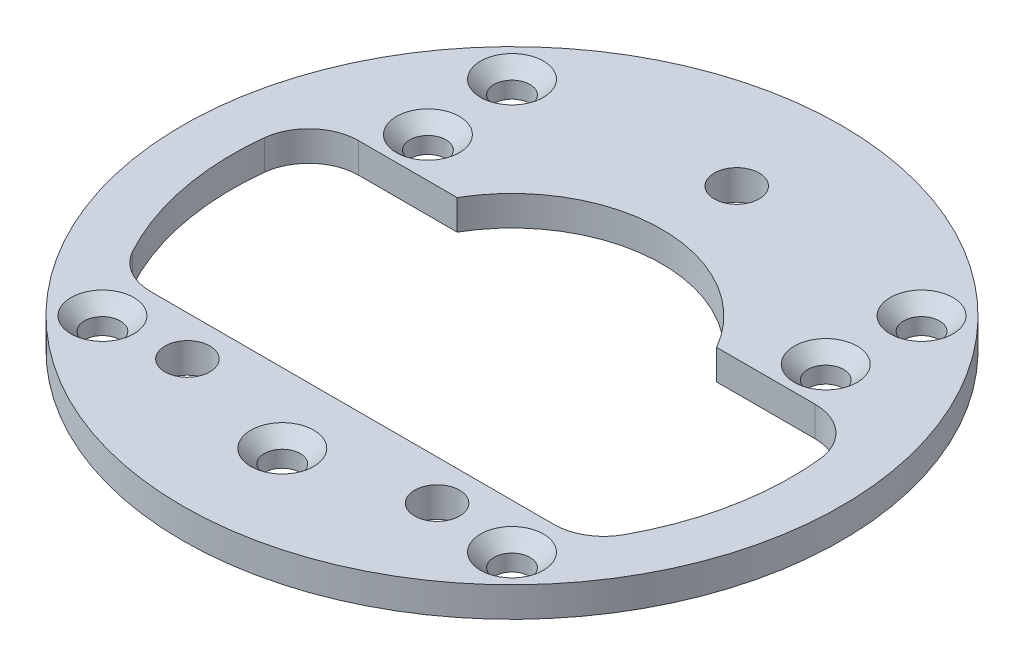
SolidWorks part; units mm, degrees
material "ABS"
ref_plane "Front Plane" through (0, 0, 0) normal (0, 0, 1) x (1, 0, 0)
ref_plane "Top Plane" through (0, 0, 0) normal (0, 1, 0) x (1, 0, 0)
ref_plane "Right Plane" through (0, 0, 0) normal (1, 0, 0) x (0, 0, -1)
sketch "Sketch1" plane through (0, 0, 0) normal (0, 1, 0) x (1, 0, 0)
  circle A0 centre (0, 0) radius 33
  circle A1 centre (0, 0) radius 28
  dimension "D1" = 66
  dimension "D2" = 5
extrude "Boss-Extrude1" add sketch "Sketch1" along normal blind 3
sketch "Sketch2" plane through (0, 3, 0) normal (0, 1, 0) x (1, 0, 0)
  line L0 (-22.9783, -16) -> (22.9783, -16)
  line L1 (-26.9768, 7.5) -> (-12.9904, 7.5)
  line L2 (0, 0) -> (7.7557, 0) construction
  line L3 (12.9904, 7.5) -> (26.9768, 7.5)
  line L4 (-20.5061, 20.5061) -> (0, 0) construction
  circle A0 centre (0, 22.5) radius 2.25 construction
  circle A1 centre (-12.5, -20) radius 2.25 construction
  circle A2 centre (12.5, -20) radius 2.25 construction
  circle A3 centre (0, -23) radius 1.5 construction
  circle A4 centre (0, 0) radius 23 construction
  circle A5 centre (-19.9186, 11.5) radius 1.5 construction
  circle A6 centre (0, 0) radius 28 construction
  circle A7 centre (19.9186, 11.5) radius 1.5 construction
  arc A8 (-12.9904, 7.5) -> (12.9904, 7.5) centre (0, 0) cw
  arc A9 (26.9768, 7.5) -> (-27.2028, 6.6339) centre (0, 0) ccw
  arc A10 (22.9783, -16) -> (-22.9783, -16) centre (0, 0) cw
  circle A12 centre (0, 0) radius 29 construction
  circle A13 centre (0, 0) radius 33 construction
  circle A14 centre (-20.5061, 20.5061) radius 1.75 construction
  circle A15 centre (20.5061, 20.5061) radius 1.75 construction
  circle A16 centre (20.5061, -20.5061) radius 1.75 construction
  circle A17 centre (-20.5061, -20.5061) radius 1.75 construction
  point P19 (0, 0)
  point P44 (0, 0)
  circle M2 centre (0, 0) radius 28
  dimension "D5" = 4.5
  dimension "D6" = 4.5
  dimension "D7" = 4.5
  dimension "D10" = 3
  dimension "D12" = 15
  dimension "D16" = 3.5
  dimension "D1" = 25
  dimension "D2" = 12.5
  dimension "D3" = 22.5
  dimension "D4" = 20
  dimension "D9" = 5
  dimension "D11" = 4
  dimension "D13" = 7
  dimension "D14" = 4
  dimension "D15" = 135
  dimension "D18" = 5
  dimension "D8" = 3
  dimension "D17" = 4
extrude "Saliente-Extruir1" add sketch "Sketch2" against normal up to surface (3 mm away) contours L1 A8 L3 M2 | L0 M2 region at (0, 3, 20.9008) region at (0, 3, -17.1389) up to face at (0, 0, 33)
sketch "Croquis1" plane through (0, 3, 0) normal (0, 1, 0) x (1, 0, 0)
  circle A0 centre (-20.5061, 20.5061) radius 1.75 construction
  circle A1 centre (-20.5061, 20.5061) radius 1.75
  circle A2 centre (0, 22.5) radius 2.25 construction
  circle A3 centre (0, 22.5) radius 2.25
  circle A4 centre (20.5061, 20.5061) radius 1.75 construction
  circle A5 centre (20.5061, 20.5061) radius 1.75
  circle A6 centre (-19.9186, 11.5) radius 1.5 construction
  circle A7 centre (-19.9186, 11.5) radius 1.5
  circle A8 centre (19.9186, 11.5) radius 1.5 construction
  circle A9 centre (19.9186, 11.5) radius 1.5
  circle A10 centre (0, -23) radius 1.5 construction
  circle A11 centre (0, -23) radius 1.5
  circle A12 centre (12.5, -20) radius 2.25 construction
  circle A13 centre (12.5, -20) radius 2.25
  circle A14 centre (-12.5, -20) radius 2.25 construction
  circle A15 centre (-12.5, -20) radius 2.25
  circle A16 centre (-20.5061, -20.5061) radius 1.75 construction
  circle A17 centre (-20.5061, -20.5061) radius 1.75
  circle A18 centre (20.5061, -20.5061) radius 1.75 construction
  circle A19 centre (20.5061, -20.5061) radius 1.75
extrude "Cortar-Extruir1" cut sketch "Croquis1" against normal up to next
hole_wizard "CSK for M3 Flat Head Machine Screw1" positions "Sketch4" profile "Sketch5" countersink size "M3" standard "ANSI Metric" end condition through all
sketch "Sketch4" plane through (0, 3, 0) normal (0, 1, 0) x (1, 0, 0)
  point P0 (-20.5061, 20.5061)
  point P3 (20.5061, 20.5061)
  point P6 (20.5061, -20.5061)
  point P9 (-20.5061, -20.5061)
sketch "Sketch5" plane through (-20.5061, 3, -20.5061) normal (1, 0, 0) x (0, 0, 1)
  line L0 (0, 0) -> (0, 3)
  line L1 (0, 3) -> (1.8, 3)
  line L2 (1.8, 3) -> (1.8, 1.35)
  line L3 (1.8, 1.35) -> (3.15, 0)
  line L5 (3.15, 0) -> (0, 0)
  line L6 (-1.8, 1.35) -> (-3.15, 0) construction
  line L11 (0, -6.35) -> (0, 107.95) construction
  dimension "Thru Hole Dia." = 3.6
  dimension "Thru Hole Depth" = 3
  dimension "Near C'Sink Dia." = 6.3
  dimension "Near C'Sink Angle" = 90
hole_wizard "CSK for M3 Flat Head Machine Screw2" positions "Sketch6" profile "Sketch7" countersink size "M3" standard "ANSI Metric" end condition through all
sketch "Sketch6" plane through (0, 3, 0) normal (0, 1, 0) x (1, 0, 0)
  point P0 (-19.9186, 11.5)
  point P3 (19.9186, 11.5)
  point P6 (0, -23)
sketch "Sketch7" plane through (-19.9186, 3, -11.5) normal (1, 0, 0) x (0, 0, 1)
  line L0 (0, 0) -> (0, 3)
  line L1 (0, 3) -> (1.8, 3)
  line L2 (1.8, 3) -> (1.8, 1.35)
  line L3 (1.8, 1.35) -> (3.15, 0)
  line L5 (3.15, 0) -> (0, 0)
  line L6 (-1.8, 1.35) -> (-3.15, 0) construction
  line L11 (0, -6.35) -> (0, 107.95) construction
  dimension "Thru Hole Dia." = 3.6
  dimension "Thru Hole Depth" = 3
  dimension "Near C'Sink Dia." = 6.3
  dimension "Near C'Sink Angle" = 90
fillet "Fillet1" radius 5 4 edges at (-26.9768, 1.5, -7.5) (26.9768, 1.5, -7.5) (22.9783, 1.5, 16) (-22.9783, 1.5, 16)
equation "\"D2@Sketch2\"=\"D1@Sketch2\"/2"
equation "\"D6@Sketch2\"=\"D5@Sketch2\""
equation "\"D7@Sketch2\"=\"D6@Sketch2\""
equation "\"D10@Sketch2\"=\"D8@Sketch2\""
